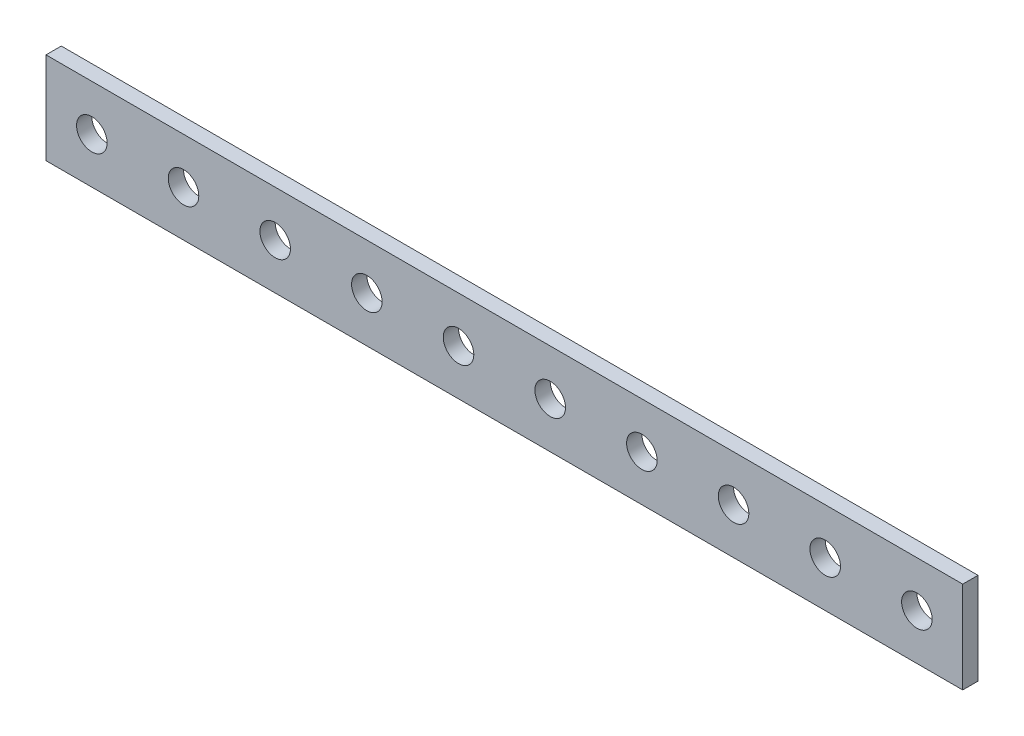
SolidWorks part; units mm, degrees
ref_plane "Front" through (0, 0, 0) normal (0, 0, 1) x (1, 0, 0)
ref_plane "Top" through (0, 0, 0) normal (0, 1, 0) x (1, 0, 0)
ref_plane "Right" through (0, 0, 0) normal (1, 0, 0) x (0, 0, -1)
sketch "Sketch1" plane through (0, 0, 0) normal (0, 0, 1) x (1, 0, 0)
  line L0 (0, 0) -> (-1.5, 0) construction
  line L1 (0, 0) -> (27, 0) construction
  line L2 (0, 0) -> (0, 1.5) construction
  line L3 (-1.5, -1.5) -> (28.5, -1.5)
  line L4 (-1.5, -1.5) -> (-1.5, 1.5)
  line L5 (-1.5, 1.5) -> (28.5, 1.5)
  line L6 (28.5, -1.5) -> (28.5, 1.5)
  line L7 (0, 0) -> (0, -1.5) construction
  line L8 (27, 0) -> (28.5, 0) construction
  circle A0 centre (0, 0) radius 0.5
  circle A1 centre (3, 0) radius 0.5
  circle A2 centre (6, 0) radius 0.5
  circle A3 centre (9, 0) radius 0.5
  circle A4 centre (12, 0) radius 0.5
  circle A5 centre (15, 0) radius 0.5
  circle A6 centre (18, 0) radius 0.5
  circle A7 centre (21, 0) radius 0.5
  circle A8 centre (24, 0) radius 0.5
  circle A9 centre (27, 0) radius 0.5
  point P29 (26.5827, 0)
  point P30 (15.9434, 0)
  point P31 (3, 0)
  point P32 (6, 0)
  point P33 (9, 0)
  point P34 (12, 0)
  point P35 (0, 0)
  point P36 (0, 0)
  point P37 (18, 0)
  point P38 (21, 0)
  point P39 (0, 0)
  point P40 (27, 0)
  point P41 (24, 0)
  point P42 (27, 0)
  dimension "SHAFT" = 1
  dimension "D2" = 1.5
  dimension "Length0" = 3
  dimension "Length1" = 3
  dimension "Length2" = 3
  dimension "Length3" = 3
  dimension "Length4" = 3
  dimension "Length5" = 3
  dimension "Length6" = 3
  dimension "Length7" = 3
  dimension "Length8" = 3
extrude "Boss-Extrude1" add sketch "Sketch1" against normal blind 0.5 contours A4 L6 L5 L4 L3 A3 A2 A1 A0 region at (13.5, 0, 0)
ref_plane "Back" through (0, 0, 0) normal (0, 0, 1) x (1, 0, 0)
ref_axis "Axis0" through (0, 0, -0.5) along (0, 0, 1)
ref_axis "Axis1" through (3, 0, -0.5) along (0, 0, 1)
ref_axis "Axis2" through (6, 0, -0.5) along (0, 0, 1)
ref_axis "Axis3" through (9, 0, -0.5) along (0, 0, 1)
ref_axis "Axis4" through (12, 0, -0.5) along (0, 0, 1)
ref_axis "Axis5" through (15, 0, -0.5) along (0, 0, 1)
ref_axis "Axis6" through (18, 0, -0.5) along (0, 0, 1)
ref_axis "Axis7" through (21, 0, -0.5) along (0, 0, 1)
ref_axis "Axis8" through (24, 0, -0.5) along (0, 0, 1)
ref_axis "Axis9" through (27, 0, -0.5) along (0, 0, 1)
equation "\"Dshaft\"= 1"
equation "\"D2@Sketch1\"=1.5 * \"SHAFT@Sketch1\""
equation "\"SHAFT\"=1"
equation "\"D1@Boss-Extrude1\"=\"SHAFT\"*0.5"
